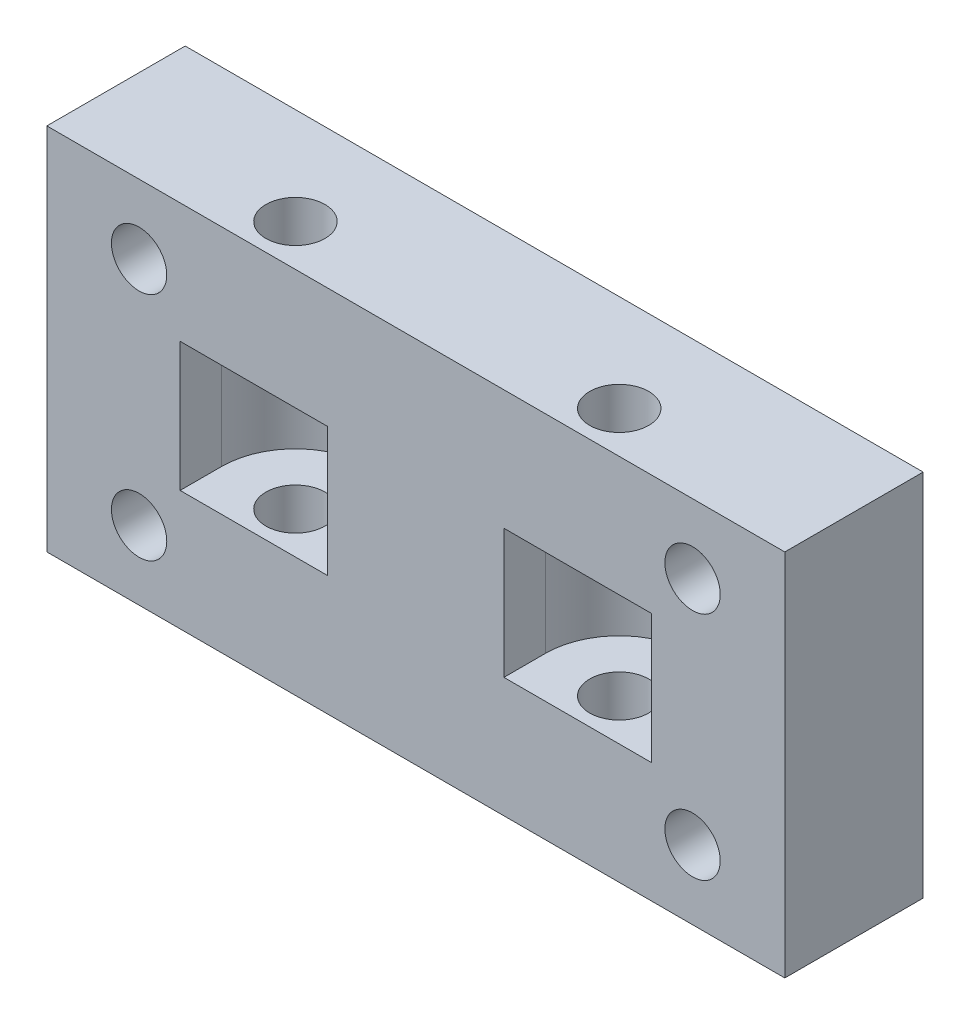
SolidWorks part; units mm, degrees
ref_plane "Front Plane" through (0, 0, 0) normal (0, 0, 1) x (1, 0, 0)
ref_plane "Top Plane" through (0, 0, 0) normal (0, 1, 0) x (1, 0, 0)
ref_plane "Right Plane" through (0, 0, 0) normal (1, 0, 0) x (0, 0, -1)
sketch "Sketch1" plane through (0, 0, 0) normal (0, 0, 1) x (1, 0, 0)
  line L2 (-25.4, -12.7) -> (-25.4, 12.7)
  line L3 (-25.4, 12.7) -> (25.4, 12.7)
  line L10 (25.4, -12.7) -> (25.4, 12.7)
  line L11 (-25.4, -12.7) -> (25.4, -12.7)
  line L14 (-25.4, 12.7) -> (25.4, -12.7) construction
  point P2 (0, 0)
  dimension "D1" = 50.8
  dimension "D2" = 25.4
extrude "Boss-Extrude1" add sketch "Sketch1" along normal blind 9.525
sketch "Sketch4" plane through (0, 0, 0) normal (0, 1, 0) x (1, 0, 0)
  line L7 (25.4, -9.525) -> (-25.4, -9.525) construction
  line L8 (-16.2242, -6.6675) -> (-16.2242, -9.525)
  line L9 (-6.0642, -6.6675) -> (-6.0643, -9.525)
  line L10 (-6.0643, -9.525) -> (-16.2242, -9.525)
  line L11 (-25.4, -9.525) -> (-25.4, 0) construction
  arc A2 (-6.0642, -6.6675) -> (-16.2242, -6.6675) centre (-11.1442, -6.6675) ccw
  dimension "D1" = 10.16
  dimension "D2" = 2.8575
  dimension "D3" = 14.2558
extrude "Cut-Extrude2" cut sketch "Sketch4" against normal mid plane 8.89
ref_plane "Plane3" through (0, 0, 0) normal (-1, 0, 0) x (0, 0, 1)
sketch "Sketch2" plane through (0, 0, 9.525) normal (0, 0, 1) x (1, 0, 0)
  line L0 (-25.4, -12.7) -> (25.4, -12.7) construction
  line L1 (-25.4, 12.7) -> (-25.4, -12.7) construction
  circle A0 centre (-19.05, 7.9375) radius 1.905
  dimension "D1" = 3.81
  dimension "D2" = 20.6375
  dimension "D3" = 6.35
extrude "Cut-Extrude1" cut sketch "Sketch2" against normal up to surface (9.525 mm away) up to face at (0, 0, 0)
sketch "Sketch5" plane through (0, 12.7, 0) normal (0, 1, 0) x (1, 0, 0)
  line L0 (25.4, -9.525) -> (-25.4, -9.525) construction
  line L1 (-25.4, -9.525) -> (-25.4, 0) construction
  circle A0 centre (-11.1442, -6.6675) radius 2.032
  dimension "D3" = 4.064
  dimension "D1" = 2.8575
  dimension "D2" = 14.2558
extrude "Cut-Extrude3" cut sketch "Sketch5" along normal blind 3.175 and the other way through all
mirror "Mirror1" about plane through (0, 0, 0) normal (0, 1, 0) of "Cut-Extrude1"
mirror "Mirror2" about plane through (0, 0, 0) normal (-1, 0, 0) of "Mirror1", "Cut-Extrude3", "Cut-Extrude2"
